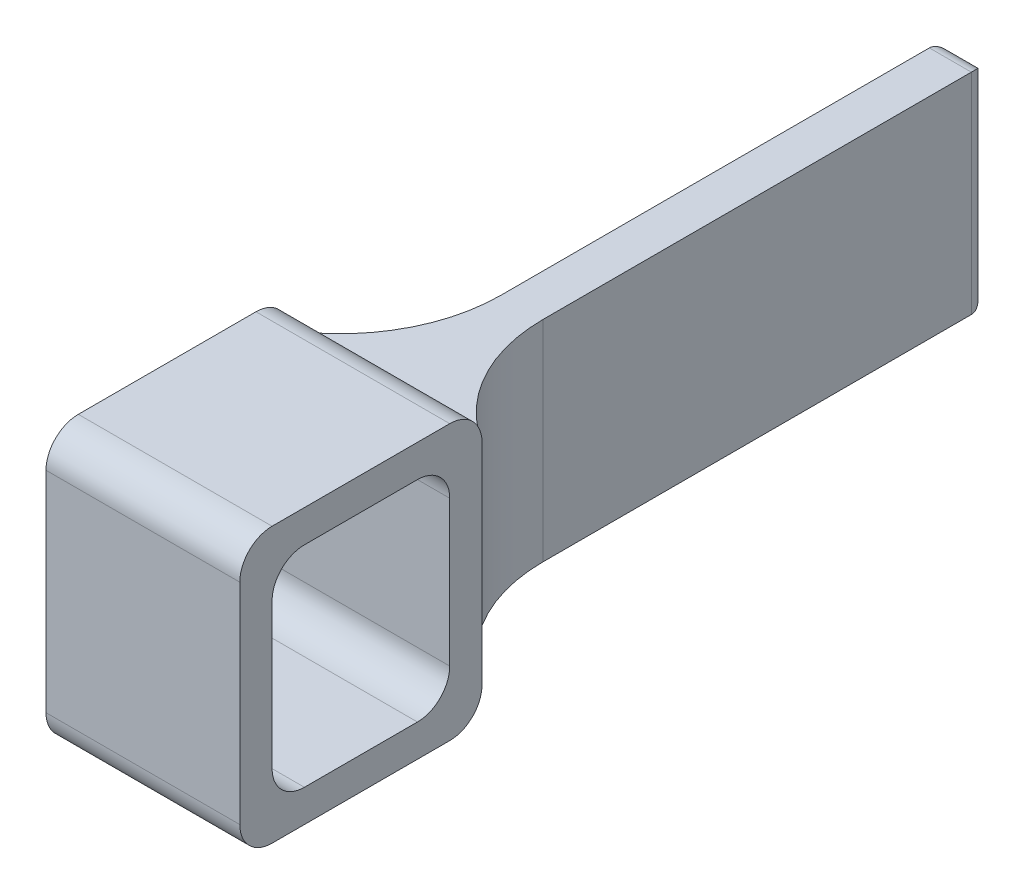
SolidWorks part; units mm, degrees
ref_plane "Plano frontal" through (0, 0, 0) normal (0, 0, 1) x (1, 0, 0)
ref_plane "Plano superior" through (0, 0, 0) normal (0, 1, 0) x (1, 0, 0)
ref_plane "Plano direito" through (0, 0, 0) normal (1, 0, 0) x (0, 0, -1)
sketch "Esboço1" plane through (-161.8028, 0, 0) normal (1, 0, 0) x (0, 0, -1)
  line L1 (384.6946, 46.9585) -> (379.1946, 46.9585)
  line L2 (385.6946, 45.9585) -> (385.6946, 39.4585)
  line L3 (384.6946, 38.4585) -> (379.1946, 38.4585)
  line L4 (378.1946, 45.9585) -> (378.1946, 39.4585)
  line L5 (381.9446, 45.7085) -> (381.9446, 39.7085) construction
  line L6 (383.4446, 45.7085) -> (380.4446, 45.7085) construction
  line L7 (380.4446, 39.7085) -> (383.4446, 39.7085) construction
  line L8 (381.9446, 46.9585) -> (381.9446, 38.4585) construction
  arc A0 (379.1946, 46.9585) -> (378.1946, 45.9585) centre (379.1946, 45.9585) ccw
  arc A1 (379.1946, 38.4585) -> (378.1946, 39.4585) centre (379.1946, 39.4585) cw
  arc A2 (385.6946, 39.4585) -> (384.6946, 38.4585) centre (384.6946, 39.4585) cw
  arc A3 (384.6946, 46.9585) -> (385.6946, 45.9585) centre (384.6946, 45.9585) cw
  point P12 (381.9446, 42.7085)
  point P13 (381.9446, 42.7085)
  point P18 (378.1946, 38.4585)
  point P21 (385.6946, 38.4585)
  point P24 (385.6946, 46.9585)
  dimension "D3" = 1
  dimension "D1" = 8.5
  dimension "D2" = 7.5
extrude "Ressalto-extrusão1" add sketch "Esboço1" along normal blind 6
sketch "Esboço2" plane through (-155.8028, 0, 0) normal (1, 0, 0) x (0, 0, -1)
  line L0 (381.9446, 46.9585) -> (381.9446, 38.4585) construction
  line L1 (380.1946, 45.9585) -> (383.6946, 45.9585)
  line L2 (379.1946, 44.9585) -> (379.1946, 40.4585)
  line L3 (380.1946, 39.4585) -> (383.6946, 39.4585)
  line L4 (384.6946, 44.9585) -> (384.6946, 40.4585)
  line L5 (384.6946, 46.9585) -> (379.1946, 46.9585) construction
  line L6 (379.1946, 38.4585) -> (384.6946, 38.4585) construction
  line L7 (381.9446, 45.9585) -> (381.9446, 39.4585) construction
  arc A0 (383.6946, 39.4585) -> (384.6946, 40.4585) centre (383.6946, 40.4585) ccw
  arc A1 (379.1946, 40.4585) -> (380.1946, 39.4585) centre (380.1946, 40.4585) ccw
  arc A2 (383.6946, 45.9585) -> (384.6946, 44.9585) centre (383.6946, 44.9585) cw
  arc A3 (380.1946, 45.9585) -> (379.1946, 44.9585) centre (380.1946, 44.9585) ccw
  point P12 (381.9446, 42.7085)
  point P13 (381.9446, 42.7085)
  point P16 (384.6946, 39.4585)
  point P21 (384.6946, 45.9585)
  point P24 (379.1946, 45.9585)
  dimension "D3" = 1
  dimension "D1" = 6.5
  dimension "D2" = 5.5
extrude "Corte-extrusão1" cut sketch "Esboço2" against normal through all
sketch "Esboço3" plane through (0, 0, -385.6946) normal (0, 0, -1) x (-1, 0, 0)
  line L0 (155.8028, 45.9585) -> (161.8028, 45.9585) construction
  line L1 (159.4528, 45.9585) -> (158.1528, 45.9585)
  line L2 (159.4528, 45.9585) -> (159.4528, 39.4585)
  line L3 (159.4528, 39.4585) -> (158.1528, 39.4585)
  line L4 (158.1528, 45.9585) -> (158.1528, 39.4585)
  line L5 (155.8028, 39.4585) -> (161.8028, 39.4585) construction
  line L6 (161.8028, 42.7085) -> (155.8028, 42.7085) construction
  line L7 (161.8028, 39.4585) -> (161.8028, 45.9585) construction
  line L8 (155.8028, 39.4585) -> (155.8028, 45.9585) construction
  line L9 (158.8028, 45.9585) -> (158.8028, 39.4585) construction
  point P16 (158.8028, 42.7085)
  point P17 (158.8028, 42.7085)
  dimension "D1" = 1.3
extrude "Ressalto-extrusão2" add sketch "Esboço3" along normal blind 18
fillet "Filete1" radius 5 2 edges at (-159.4528, 42.7085, -385.6946) (-158.1528, 42.7085, -385.6946)
fillet "Filete3" radius 0.5 4 edges at (-159.4528, 42.7085, -403.6946) (-158.1528, 42.7085, -403.6946) (-158.8028, 39.4585, -403.6946) (-158.8028, 45.9585, -403.6946)
